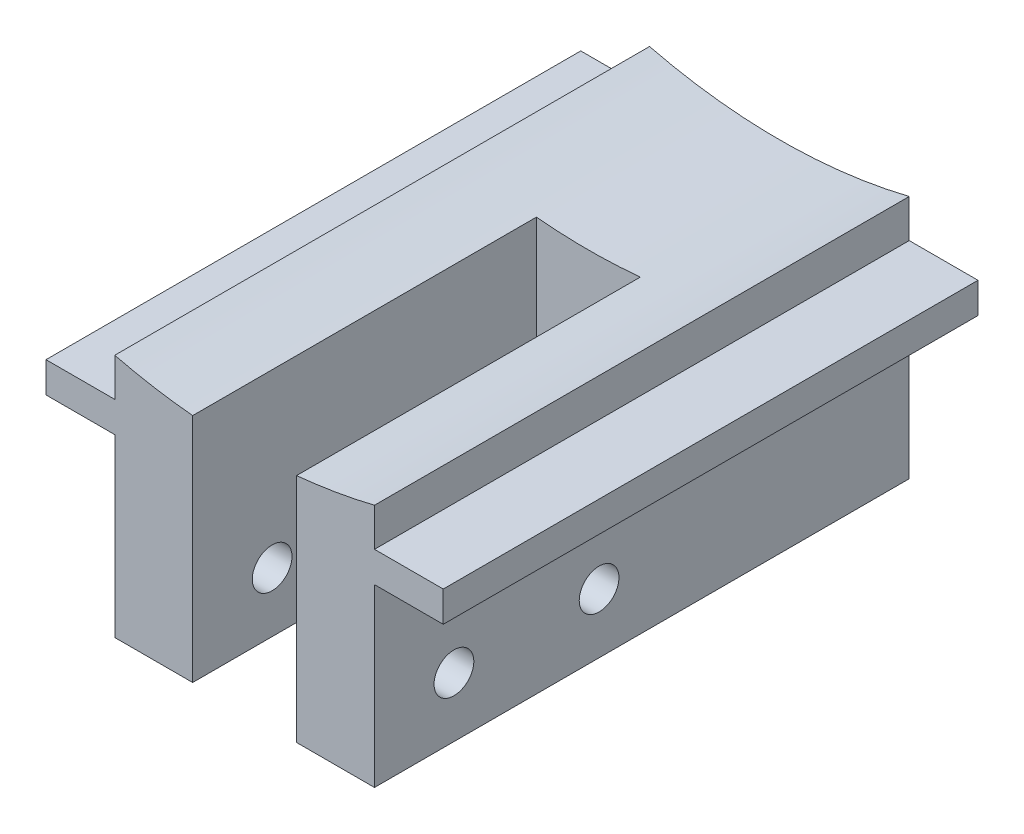
SolidWorks part; units mm, degrees
ref_plane "前基準面" through (0, 0, 0) normal (0, 0, 1) x (1, 0, 0)
ref_plane "上基準面" through (0, 0, 0) normal (0, 1, 0) x (1, 0, 0)
ref_plane "右基準面" through (0, 0, 0) normal (1, 0, 0) x (0, 0, -1)
ref_axis "基準軸1" through (0, -55, 0) along (0, 1, 0)
ref_axis "基準軸2" through (-88.99, 0, 0) along (1, 0, 0)
ref_axis "基準軸3" through (0, 0, 55) along (0, 0, -1)
sketch "草圖2" plane through (0, 0, 0) normal (0, 0, 1) x (1, 0, 0)
  line L1 (-8.5, -8) -> (8.5, -8)
  line L2 (-8.5, -8) -> (-8.5, 8)
  line L4 (8.5, -8) -> (8.5, 8)
  line L5 (9.35, 0) -> (-9.35, 0) construction
  line L6 (0, -55) -> (0, 55) construction
  arc A0 (-8.5, 8) -> (8.5, 8) centre (0, 42.4674) ccw
  point P7 (-8.5, 0)
  dimension "D3" = 71
  dimension "D4" = 8.5
  dimension "D1" = 16
  dimension "D2" = 17
extrude "填料-伸長1" add sketch "草圖2" against normal blind 35
sketch "草圖3" plane through (0, 0, 0) normal (0, 0, 1) x (1, 0, 0)
  line L0 (-8.5, -8) -> (8.5, -8) construction
  line L1 (-3.4, -8) -> (3.4, -8)
  line L2 (-3.4, -8) -> (-3.4, 7.1306)
  line L4 (3.4, -8) -> (3.4, 7.1306)
  line L5 (0, -8.8) -> (0, 8.8) construction
  arc A0 (-3.4, 7.1306) -> (3.4, 7.1306) centre (0, 42.4674) ccw
  arc A1 (-8.5, 8) -> (8.5, 8) centre (0, 42.4674) ccw construction
  point P6 (0, -8)
  dimension "D2" = 71
  dimension "D1" = 6.8
extrude "除料-伸長1" cut sketch "草圖3" against normal blind 22.5
sketch "草圖5" plane through (-8.5, 0, 0) normal (-1, 0, 0) x (0, 0, 1)
  line L0 (-35, -8) -> (0, -8) construction
  line L1 (0, -8.8) -> (0, 8.8) construction
  circle A0 centre (-5.2, -4.1) radius 1.3
  circle A1 centre (-14.7, -4.1) radius 1.3
  dimension "D1" = 2.6
  dimension "D2" = 2.6
  dimension "D3" = 3.9
  dimension "D4" = 5.2
  dimension "D5" = 9.5
extrude "除料-伸長3" cut sketch "草圖5" against normal through all
sketch "草圖6" plane through (0, 0, 0) normal (0, 0, 1) x (1, 0, 0)
  line L0 (8.5, -8) -> (8.5, 8) construction
  line L1 (8.5, 5.5) -> (13, 5.5)
  line L2 (8.5, 5.5) -> (8.5, 3.5)
  line L3 (8.5, 3.5) -> (13, 3.5)
  line L4 (13, 5.5) -> (13, 3.5)
  line L5 (0, -8.8) -> (0, 8.8) construction
  dimension "D1" = 2.5
  dimension "D2" = 2
  dimension "D3" = 13
extrude "填料-伸長2" add sketch "草圖6" against normal blind 35
mirror "鏡射1" about plane through (0, 0, 0) normal (1, 0, 0) of "填料-伸長2"
